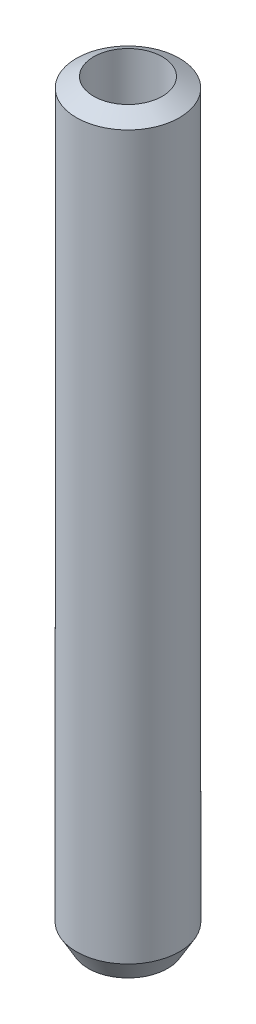
SolidWorks part; units mm, degrees
ref_plane "Front Plane" through (0, 0, 0) normal (0, 0, 1) x (1, 0, 0)
ref_plane "Top Plane" through (0, 0, 0) normal (0, 1, 0) x (1, 0, 0)
ref_plane "Right Plane" through (0, 0, 0) normal (1, 0, 0) x (0, 0, -1)
sketch "Sketch1" plane through (0, 0, 0) normal (0, 1, 0) x (1, 0, 0)
  circle A0 centre (0, 0) radius 22.5
  dimension "SHAFT_OD" = 45
extrude "Boss-Extrude1" add sketch "Sketch1" along normal blind 329.7358
sketch "Sketch2" plane through (0, 0, 0) normal (0, 1, 0) x (1, 0, 0)
  circle A0 centre (0, 0) radius 14.9959
  dimension "BORE_D" = 29.9917
extrude "Cut-Extrude1" cut sketch "Sketch2" along normal through all
chamfer "Chamfer1" distance 5.1478 angle 60 2 edges at (0, 329.7358, 22.5) (0, 0, 22.5) first distance on face at (0, 329.7358, 22.5) first distance on face at (0, 0, 14.9959)
